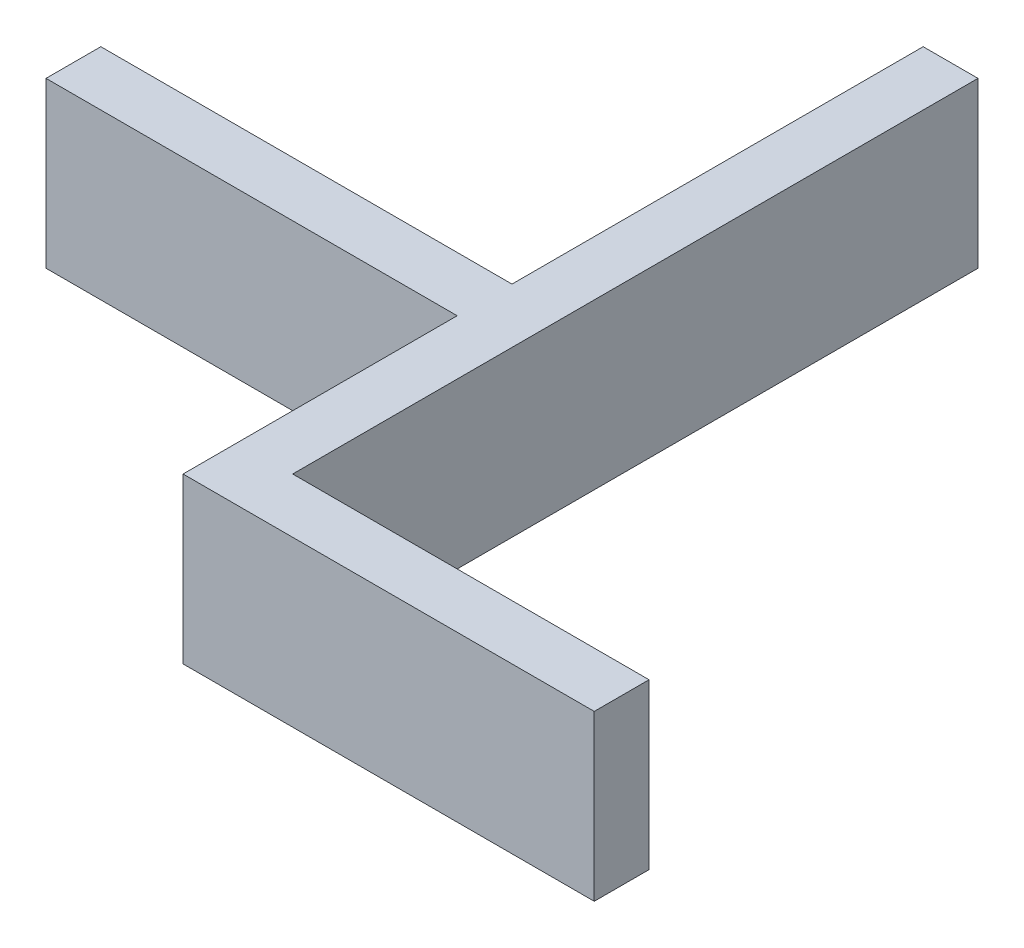
SolidWorks part; units mm, degrees
ref_plane "Plan de face" through (0, 0, 0) normal (0, 0, 1) x (1, 0, 0)
ref_plane "Plan de dessus" through (0, 0, 0) normal (0, 1, 0) x (1, 0, 0)
ref_plane "Plan de droite" through (0, 0, 0) normal (1, 0, 0) x (0, 0, -1)
sketch "Esquisse1" plane through (0, 0, 0) normal (1, 0, 0) x (0, 0, -1)
  line L0 (-27.7784, -25.7573) -> (-27.7784, -31.7573)
  line L1 (-29.7784, -25.7573) -> (-2.7784, -25.7573)
  line L2 (-29.7784, -25.7573) -> (-29.7784, -31.7573)
  line L3 (-29.7784, -31.7573) -> (-2.7784, -31.7573)
  line L4 (-2.7784, -25.7573) -> (-2.7784, -31.7573)
  line L5 (-19.7784, -25.7573) -> (-19.7784, -31.7573)
  line L6 (-17.7784, -25.7573) -> (-17.7784, -31.7573)
  dimension "D1" = 25
  dimension "D2" = 2
  dimension "D3" = 2
  dimension "D4" = 8
  dimension "D5" = 6
extrude "Boss.-Extru.2" add sketch "Esquisse1" along normal blind 2 contours L6 L1 L5 L3 | L1 L6 L3 L4 | L5 L1 L0 L3 region at (0, -28.7573, 23.7784) region at (0, -28.7573, 18.7784) region at (0, -28.7573, 10.2784)
extrude "Boss.-Extru.3" add sketch "Esquisse1<4>" along normal blind 15 contours L2 L3 L0 L1 region at (0, -28.7573, 28.7784)
sketch "Esquisse1<4>" plane through (0, 0, 0) normal (1, 0, 0) x (0, 0, -1) same geometry as "Esquisse1"
extrude "Boss.-Extru.4" add sketch "Esquisse1<5>" against normal blind 15 contours L6 L1 L5 L3 region at (0, -28.7573, 18.7784)
sketch "Esquisse1<5>" plane through (0, 0, 0) normal (1, 0, 0) x (0, 0, -1) same geometry as "Esquisse1"
